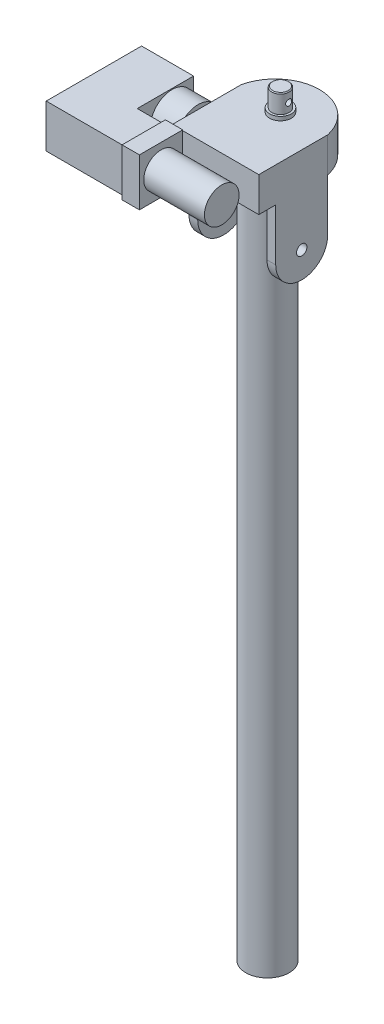
SolidWorks part; units mm, degrees
ref_plane "Alzado" through (0, 0, 0) normal (0, 0, 1) x (1, 0, 0)
ref_plane "Planta" through (0, 0, 0) normal (0, 1, 0) x (1, 0, 0)
ref_plane "Vista lateral" through (0, 0, 0) normal (1, 0, 0) x (0, 0, -1)
sketch "Croquis1" plane through (0, 0, 0) normal (0, 1, 0) x (1, 0, 0)
  line L0 (0, -60) -> (0, 19.5256) construction
  line L1 (-50, -60) -> (50, -60) construction
  line L2 (-50, -60) -> (-50, 60) construction
  line L3 (-50, 60) -> (50, 60) construction
  line L4 (50, -60) -> (50, 60) construction
  line L5 (-50, -60) -> (50, 60) construction
  line L6 (-50, 60) -> (50, -60) construction
  line L7 (-50, 19.5256) -> (-50, -60)
  line L8 (-50, -60) -> (50, -60)
  line L9 (50, -60) -> (50, 19.5256)
  arc A2 (-50, 19.5256) -> (50, 19.5256) centre (0, 8.8791) cw
  point P0 (0, 0)
extrude "Saliente-Extruir2" add sketch "Croquis1" along normal blind 40
sketch "Croquis2" plane through (0, 40, 0) normal (0, 1, 0) x (1, 0, 0)
  line L0 (0, -60) -> (0, 15) construction
  line L1 (-50, -60) -> (50, -60) construction
  circle A0 centre (0, 15) radius 12.5
extrude "Saliente-Extruir3" add sketch "Croquis2" along normal blind 4.5
sketch "Croquis3" plane through (0, 44.5, 0) normal (0, 1, 0) x (1, 0, 0)
  circle A0 centre (0, 15) radius 10
extrude "Saliente-Extruir4" add sketch "Croquis3" along normal blind 21.5
sketch "Croquis4" plane through (0, 0, 0) normal (1, 0, 0) x (0, 0, -1)
  line L0 (15, 66) -> (15, 54.5) construction
  line L1 (25, 66) -> (5, 66) construction
  circle A0 centre (15, 54.5) radius 3.5
extrude "Cortar-Extruir1" cut sketch "Croquis4" against normal blind 21.5 and the other way blind 21.5
fillet "Chaflán1" radius 1 1 edges at (0, 66, -5) type face fillet profile chamfer first side face at (0, 66, -5) second side face at (0, 66, -5)
sketch "Croquis5" plane through (-50, 0, 0) normal (-1, 0, 0) x (0, 0, 1)
  line L0 (60, 20) -> (30, 20) construction
  line L1 (60, 40) -> (60, 0) construction
  circle A0 centre (30, 20) radius 25
extrude "Saliente-Extruir5" add sketch "Croquis5" along normal blind 30
sketch "Croquis6" plane through (-80, 0, 0) normal (-1, 0, 0) x (0, 0, 1)
  line L0 (5.2509, 16.4667) -> (5.2509, 46.1101) construction
  line L1 (5.2509, 46.1101) -> (115.2509, 46.1101) construction
  line L2 (115.2509, 46.1101) -> (115.2509, -3.8899) construction
  line L4 (5.2509, 46.1101) -> (115.2509, 46.1101)
  line L5 (5.2509, 46.1101) -> (5.2509, -3.8899)
  line L6 (5.2509, -3.8899) -> (115.2509, -3.8899)
  line L7 (115.2509, 46.1101) -> (115.2509, -3.8899)
  circle A0 centre (30, 20) radius 25 construction
extrude "Saliente-Extruir6" add sketch "Croquis6" along normal blind 60
sketch "Croquis9" plane through (-80, 0, 0) normal (1, 0, 0) x (0, 0, -1)
sketch "Croquis10" plane through (-80, 0, 0) normal (1, 0, 0) x (0, 0, -1)
  line L0 (-37.3671, -3.8899) -> (-115.2509, -3.8899) construction
  line L1 (-115.2509, 46.1101) -> (-70.2509, 46.1101)
  line L2 (-115.2509, 46.1101) -> (-115.2509, -3.8899)
  line L3 (-115.2509, -3.8899) -> (-70.2509, -3.8899)
  line L4 (-70.2509, 46.1101) -> (-70.2509, -3.8899)
extrude "Saliente-Extruir7" add sketch "Croquis10" along normal blind 30
sketch "Croquis12" plane through (-50, 0, 0) normal (1, 0, 0) x (0, 0, -1)
  line L0 (-115.2509, 46.1101) -> (-70.2509, -3.8899) construction
  line L2 (-117.7509, -6.3899) -> (-67.7509, -6.3899)
  line L3 (-117.7509, -6.3899) -> (-117.7509, 48.6101)
  line L4 (-117.7509, 48.6101) -> (-67.7509, 48.6101)
  line L5 (-67.7509, -6.3899) -> (-67.7509, 48.6101)
  line L6 (-117.7509, -6.3899) -> (-67.7509, 48.6101) construction
  line L7 (-117.7509, 48.6101) -> (-67.7509, -6.3899) construction
  point P4 (-92.7509, 21.1101)
extrude "Saliente-Extruir8" add sketch "Croquis12" along normal blind 20
sketch "Croquis13" plane through (-30, 0, 0) normal (1, 0, 0) x (0, 0, -1)
  line L0 (-67.7509, 48.6101) -> (-117.7509, -6.3899) construction
  circle A0 centre (-92.7509, 21.1101) radius 20
extrude "Saliente-Extruir9" add sketch "Croquis13" along normal blind 70
sketch "Croquis14" plane through (0, 0, 0) normal (0, -1, 0) x (1, 0, 0)
  line L0 (-50, 60) -> (-40, 60) construction
  line L1 (-50, 60) -> (50, 60) construction
  line L2 (-50, -19.5256) -> (-40, -19.5256) construction
  line L3 (-40, -19.5256) -> (-40, 40.4744) construction
  line L4 (-50, -19.5256) -> (-40, -19.5256)
  line L5 (-40, -19.5256) -> (-40, 40.4744)
  line L6 (-40, 40.4744) -> (-50, 40.4744)
  line L7 (-50, 40.4744) -> (-50, -19.5256)
extrude "Saliente-Extruir10" add sketch "Croquis14" along normal blind 90
mirror "Simetría1" about plane through (0, 0, 0) normal (1, 0, 0) of "Saliente-Extruir10"
sketch "Croquis15" plane through (-50, 0, 0) normal (-1, 0, 0) x (0, 0, 1)
  line L0 (10.4744, -90) -> (10.4744, -60) construction
  line L1 (40.4744, -90) -> (-19.5256, -90) construction
  line L3 (40.4744, -90) -> (40.4744, -2.6999) construction
  line L4 (-19.5256, -90) -> (-19.5256, 0) construction
  line L5 (40.4744, -60) -> (40.4744, -90)
  line L6 (40.4744, -90) -> (-19.5256, -90)
  line L7 (-19.5256, -90) -> (-19.5256, -60)
  arc A0 (40.4744, -60) -> (-19.5256, -60) centre (10.4744, -60) cw
  circle A1 centre (10.4744, -60) radius 6
  line M11 (-19.5256, 0) -> (-19.5256, -90)
  line M12 (-19.5256, -90) -> (40.4744, -90)
  line M13 (40.4744, -90) -> (40.4744, -2.6999)
extrude "Cortar-Extruir4" cut sketch "Croquis15" against normal blind 136 contours A0 M12 M11 | A1 | A0 L6 M13 region at (-50, -83.299, -12.8246) region at (-50, -83.299, 33.7733) region at (-50, -60, 10.4744)
sketch "Croquis16" plane through (0, 0, 0) normal (0, -1, 0) x (-1, 0, 0)
  circle A0 centre (0, 0) radius 25
extrude "Saliente-Extruir11" add sketch "Croquis16" along normal blind 800
